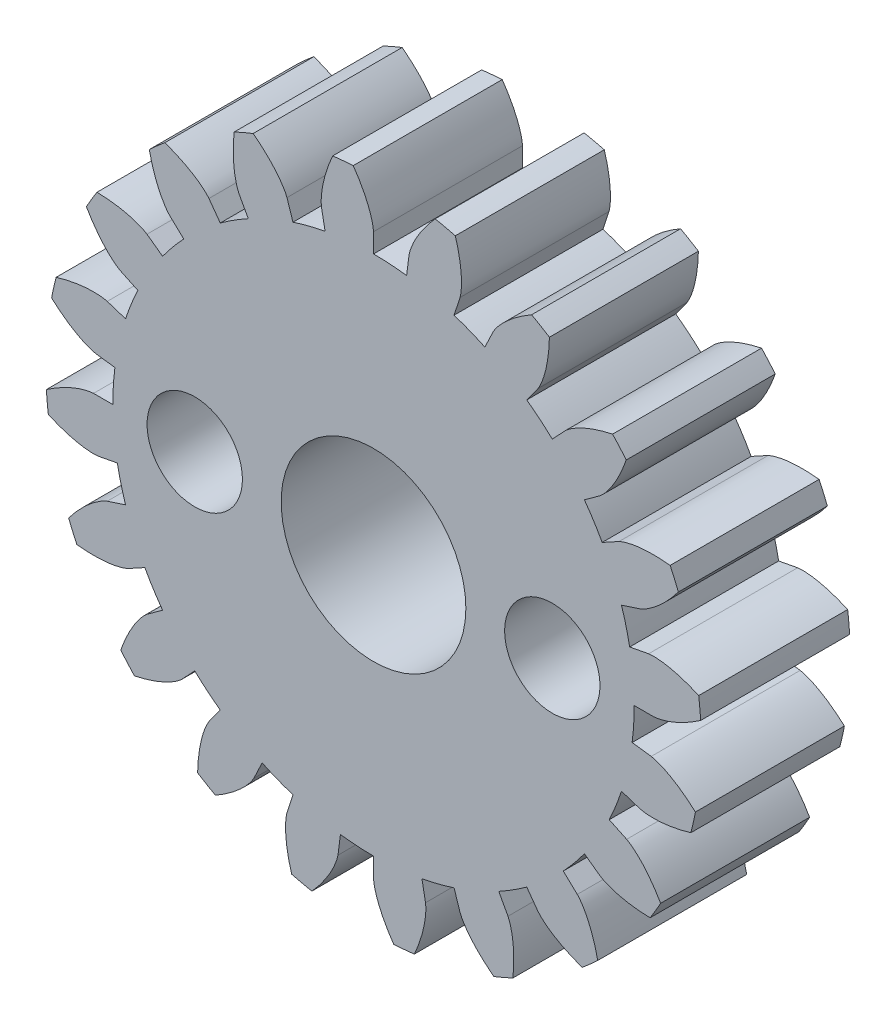
SolidWorks part; units mm, degrees
ref_plane "正面" through (0, 0, 0) normal (0, 0, 1) x (1, 0, 0)
ref_plane "平面" through (0, 0, 0) normal (0, 1, 0) x (1, 0, 0)
ref_plane "右側面" through (0, 0, 0) normal (1, 0, 0) x (0, 0, -1)
sketch "ｽｹｯﾁ1" plane through (0, 0, 0) normal (0, 0, 1) x (1, 0, 0)
  line L0 (9.3969, 0) -> (0, 0)
  line L1 (0, 0) -> (100, -6.3726)
  circle A0 centre (0, 0) radius 9.3969
  circle A1 centre (0, 0) radius 10
  circle A2 centre (0, 0) radius 11
  circle A3 centre (0, 0) radius 8.75
  spline S0 degree 4 poles (9.3969, 0) (9.4259, 0.0013) (9.5068, 0.0086) (9.6592, 0.038) (9.9017, 0.1071) (10.2056, 0.2275) (10.5805, 0.4168) (10.9966, 0.6798) (11.4254, 1.0092) (11.8545, 1.4037) (12.2511, 1.8306) (12.616, 2.2849) (12.9662, 2.7861) (13.3576, 3.4341) (13.76, 4.243) (14.1381, 5.2218) (14.4486, 6.3461) (14.655, 7.4931) (14.7613, 8.6549) (14.7739, 9.8189) (14.6944, 10.9842) (14.5324, 12.1339) (14.2838, 13.2803) (14.0074, 14.248) (13.7112, 15.0928) (13.4766, 15.689) (13.2501, 16.2125) (13.0922, 16.5556) (12.8604, 17.0353) (12.672, 17.3913) (12.4808, 17.7466) (12.3773, 17.9221) (12.3126, 18.0362) knots 0 0 0 0 0 0.005604 0.015718 0.02996 0.048734 0.068727 0.096889 0.125051 0.153212 0.181374 0.209535 0.237696 0.271429 0.327752 0.384075 0.440398 0.496721 0.553044 0.609367 0.66569 0.722013 0.778336 0.834659 0.86282 0.890982 0.909091 0.931818 0.954545 0.977273 1 1 1 1 1 construction
  spline S1 degree 4 poles (9.3969, 0) (9.4259, 0.0013) (9.5068, 0.0086) (9.6592, 0.038) (9.9017, 0.1071) (10.2056, 0.2275) (10.5805, 0.4168) (10.9966, 0.6798) (11.4254, 1.0092) (11.8545, 1.4037) (12.2511, 1.8306) (12.616, 2.2849) (12.9662, 2.7861) (13.3576, 3.4341) (13.76, 4.243) (14.1381, 5.2218) (14.4486, 6.3461) (14.655, 7.4931) (14.7613, 8.6549) (14.7739, 9.8189) (14.6944, 10.9842) (14.5324, 12.1339) (14.2838, 13.2803) (14.0074, 14.248) (13.7112, 15.0928) (13.4766, 15.689) (13.3031, 16.0901) (13.2141, 16.2882) (13.1787, 16.3656) knots 0 0 0 0 0 0.005604 0.015718 0.02996 0.048734 0.068727 0.096889 0.125051 0.153212 0.181374 0.209535 0.237696 0.271429 0.327752 0.384075 0.440398 0.496721 0.553044 0.609367 0.66569 0.722013 0.778336 0.834659 0.86282 0.890982 0.909091 0.909091 0.909091 0.909091 0.909091
  point P11 (9.9989, 0.149)
  point P12 (9.9798, -0.636)
  dimension "D1" = 20
  dimension "D2" = 18.7939
  dimension "D3" = 22
  dimension "D4" = 17.5
  dimension "D6" = 100
  dimension "D5" = 0.7854
extrude "ﾎﾞｽ - 押し出し1" add sketch "ｽｹｯﾁ1" along normal blind 5 contours A2
extrude "ｶｯﾄ - 押し出し1" cut sketch "ｽｹｯﾁ1<4>" along normal blind 5 contours S1 A1 L1 A2 | S1 A0 L1 A1 | A3 L1 A0 L0 region at (9.0712, -0.2887, 0) region at (9.7067, -0.2776, 0) region at (10.5412, -0.1277, 0)
sketch "ｽｹｯﾁ1<4>" plane through (0, 0, 0) normal (0, 0, 1) x (1, 0, 0) same geometry as "ｽｹｯﾁ1"
mirror "ﾐﾗｰ1" about plane through (0, 0, 5) normal (0.0636, 0.998, 0) of "ｶｯﾄ - 押し出し1"
pattern_circular "円形ﾊﾟﾀｰﾝ10" count 20 over 360 about axis through (0, 0, 5) along (0, 0, -1) of "ﾐﾗｰ1", "ｶｯﾄ - 押し出し1"
sketch "ｽｹｯﾁ2" plane through (0, 0, 5) normal (0, 0, 1) x (1, 0, 0)
  circle A0 centre (0, 0) radius 3.1
  dimension "D1" = 6.2
extrude "ｶｯﾄ - 押し出し2" cut sketch "ｽｹｯﾁ2" against normal blind 10
sketch "ｽｹｯﾁ3" plane through (0, 0, 0) normal (0, 0, -1) x (-1, 0, 0)
  line L1 (0, 2.75) -> (0, -2.75) construction
  circle A0 centre (-6, 0) radius 1.6
  circle A5 centre (6, 0) radius 1.6
  dimension "D1" = 3.2
  dimension "D2" = 6
extrude "ｶｯﾄ - 押し出し3" cut sketch "ｽｹｯﾁ3" against normal blind 5
equation "\"モジュール\"= 1"
equation "\"歯数\"= 20"
equation "\"圧力角\"= 20"
equation "\"歯幅\"= 5"
equation "\"基準円直径\"= \"歯数\" * \"モジュール\""
equation "\"基礎円直径\"= \"基準円直径\" * cos ( \"圧力角\" )"
equation "\"歯先円直径\"= \"基準円直径\" + \"モジュール\" * 2"
equation "\"歯底円直径\"= \"基準円直径\" - \"モジュール\" * 2.5"
equation "\"D1@ｽｹｯﾁ1\"=\"基準円直径\""
equation "\"D3@ｽｹｯﾁ1\"=\"歯先円直径\""
equation "\"D1@ﾎﾞｽ - 押し出し1\"=\"歯幅\""
equation "\"D1@円形ﾊﾟﾀｰﾝ10\"=\"歯数\""
equation "\"D4@ｽｹｯﾁ1\"=\"歯底円直径\""
equation "\"D5@ｽｹｯﾁ1\"=\"モジュール\"*pi/4"
equation "\"D2@ｽｹｯﾁ1\"=\"基礎円直径\""
equation "\"D1@ｶｯﾄ - 押し出し3\"=\"歯幅\""
